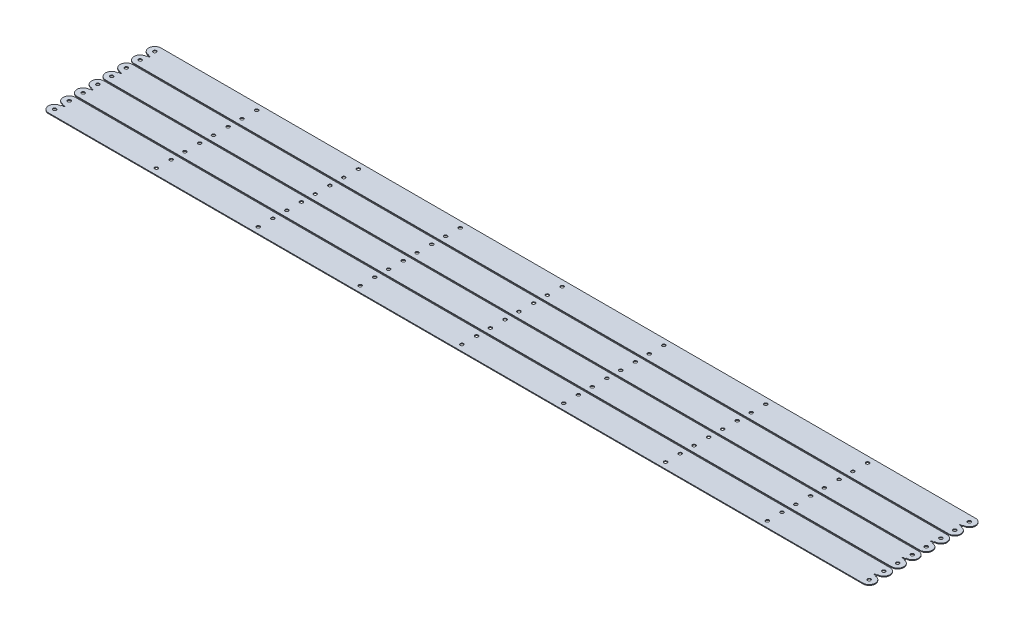
SolidWorks part; units mm, degrees
ref_plane "Front Plane" through (0, 0, 0) normal (0, 0, 1) x (1, 0, 0)
ref_plane "Top Plane" through (0, 0, 0) normal (0, 1, 0) x (1, 0, 0)
ref_plane "Right Plane" through (0, 0, 0) normal (1, 0, 0) x (0, 0, -1)
sketch "Sketch1" plane through (0, 0, 0) normal (0, 1, 0) x (1, 0, 0)
  line L0 (-500, 0) -> (500, 0) construction
  line L5 (-500, 7.5) -> (500, 7.5) construction
  line L6 (-500, 7.5) -> (-500, -7.5) construction
  line L19 (-500, -7.5) -> (500, -7.5)
  line L25 (500, 7.5) -> (500, -7.5) construction
  line L53 (-500, 7.5) -> (500, -7.5) construction
  line L95 (-500, -7.5) -> (500, 7.5) construction
  line L197 (-507.433, -1) -> (-507.5, -1)
  line L198 (-507.5, -1) -> (-507.5, 1)
  line L200 (-507.5, 1) -> (-507.433, 1)
  line L201 (-500, 7.5) -> (-500, 10.5) construction
  line L202 (0, 0) -> (0, 18) construction
  line L203 (500, 7.5) -> (500, 10.5) construction
  line L204 (500, 25.5) -> (-500, 25.5)
  line L205 (500, 25.5) -> (500, 10.5) construction
  line L206 (500, 10.5) -> (-500, 10.5) construction
  line L207 (-500, 25.5) -> (-500, 10.5) construction
  line L208 (500, 25.5) -> (-500, 10.5) construction
  line L209 (500, 10.5) -> (-500, 25.5) construction
  line L210 (-497, 8.5) -> (-497, 9.5)
  line L211 (500, 18) -> (-500, 18) construction
  line L212 (-500, 7.5) -> (-500, 8.5)
  line L213 (-500, 8.5) -> (-497, 8.5)
  line L214 (-497, 9.5) -> (-500, 9.5)
  line L215 (-500, 9.5) -> (-500, 10.5)
  line L216 (500, 10.5) -> (500, 9.5)
  line L217 (500, 9.5) -> (497, 9.5)
  line L218 (497, 9.5) -> (497, 8.5)
  line L219 (497, 8.5) -> (500, 8.5)
  line L220 (500, 8.5) -> (500, 7.5)
  line L221 (500, 9) -> (497, 9) construction
  line L222 (497, 9) -> (-497, 9) construction
  line L223 (-497, 9) -> (-500, 9) construction
  circle A70 centre (0, 0) radius 2
  arc A71 (-500, 7.5) -> (-500, -7.5) centre (-500, 0) ccw construction
  arc A72 (500, -7.5) -> (500, 7.5) centre (500, 0) ccw construction
  circle A73 centre (125, 0) radius 2
  circle A74 centre (250, 0) radius 2
  circle A75 centre (375, 0) radius 2
  circle A76 centre (500, 0) radius 2
  circle A77 centre (-125, 0) radius 2
  circle A78 centre (-250, 0) radius 2
  circle A79 centre (-375, 0) radius 2
  circle A80 centre (-500, 0) radius 2
  arc A81 (-500, 25.5) -> (-500, 10.5) centre (-500, 18) ccw
  arc A82 (500, 10.5) -> (500, 25.5) centre (500, 18) ccw
  arc A83 (500, -7.5) -> (500, 7.5) centre (500, 0) ccw
  arc A84 (-500, -7.5) -> (-507.433, -1) centre (-500, 0) cw
  arc A85 (-507.433, 1) -> (-500, 7.5) centre (-500, 0) cw
  circle A86 centre (0, 18) radius 2
  circle A87 centre (125, 18) radius 2
  circle A88 centre (250, 18) radius 2
  circle A89 centre (375, 18) radius 2
  circle A90 centre (500, 18) radius 2
  circle A91 centre (-125, 18) radius 2
  circle A92 centre (-250, 18) radius 2
  circle A93 centre (-375, 18) radius 2
  circle A94 centre (-500, 18) radius 2
  point P29 (-507.5, 0)
  dimension "D1" = 1000
  dimension "D3" = 4
  dimension "D7" = 5
  dimension "D9" = 1
  dimension "D2" = 5
  dimension "D5" = 2
  dimension "D6" = 15
  dimension "D10" = 3
  dimension "D13" = 125
  dimension "D14" = 125
  dimension "D15" = 33
  dimension "D8" = 5
  dimension "D11" = 3
  dimension "D12" = 125
extrude "Boss-Extrude1" add sketch "Sketch1" along normal blind 1 contours L219 L213 A70 A77 A78 region at (-0.0007, 0, -9)
pattern_linear "LPattern2" count 4 spacing 35 along (0, 0, -1) of "Boss-Extrude1"
